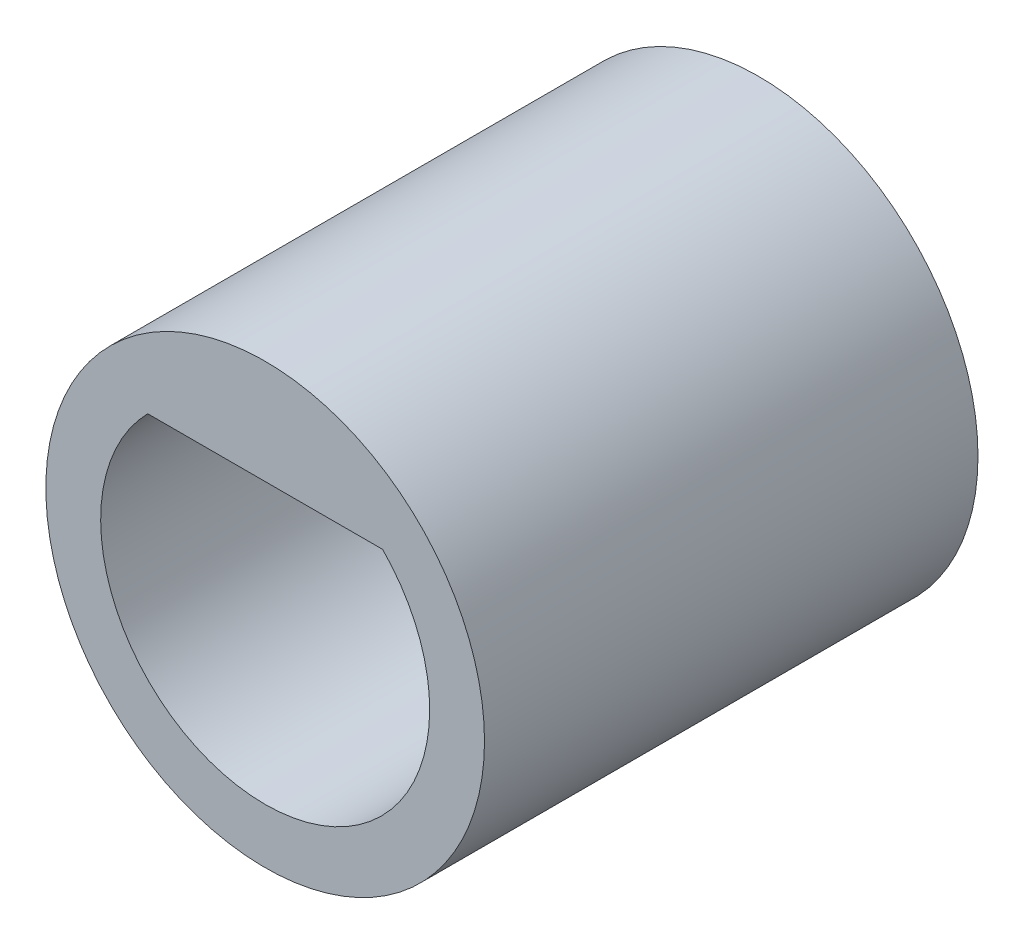
SolidWorks part; units mm, degrees
ref_plane "Plan de face" through (0, 0, 0) normal (0, 0, 1) x (1, 0, 0)
ref_plane "Plan de dessus" through (0, 0, 0) normal (0, 1, 0) x (1, 0, 0)
ref_plane "Plan de droite" through (0, 0, 0) normal (1, 0, 0) x (0, 0, -1)
sketch "Esquisse1" plane through (0, 0, 0) normal (0, 0, 1) x (1, 0, 0)
  line L0 (-2.1424, 2.1) -> (2.1424, 2.1)
  line L1 (-0.9885, -3) -> (1.037, -3) construction
  circle A0 centre (0, 0) radius 4
  arc A1 (-2.1424, 2.1) -> (2.1424, 2.1) centre (0, 0) ccw
  dimension "D1" = 8
  dimension "D2" = 6
  dimension "D3" = 5.1
extrude "Boss.-Extru.1" add sketch "Esquisse1" along normal blind 9
